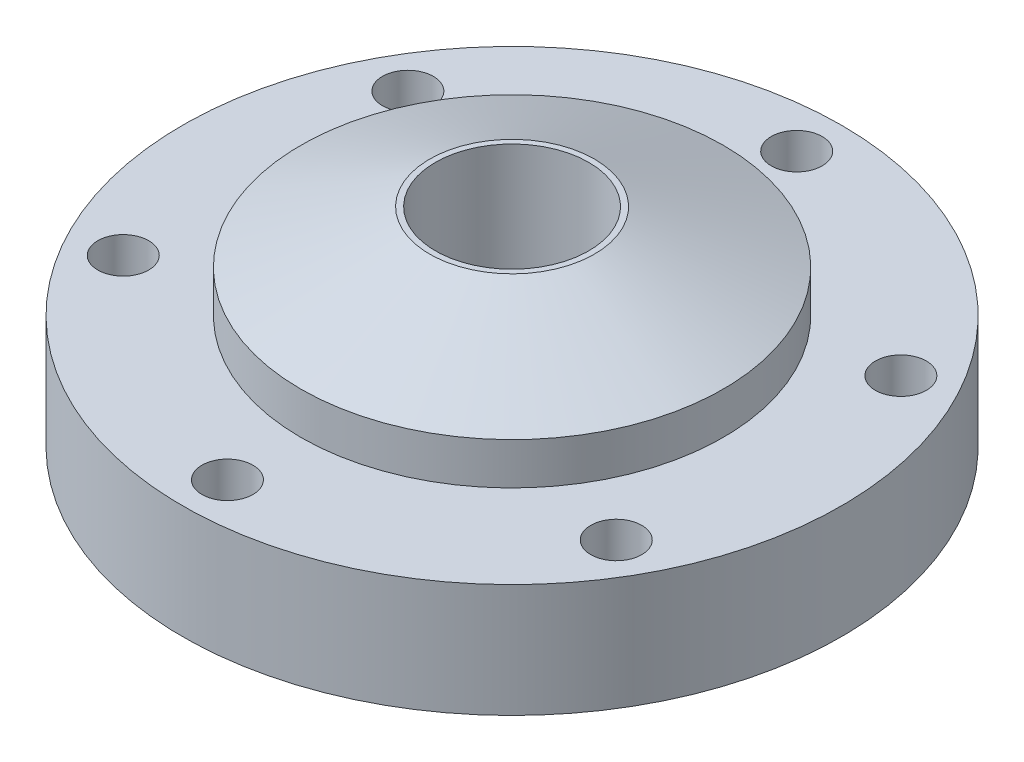
SolidWorks part; units mm, degrees
material "Hollow 3D Print"
ref_plane "Front Plane" through (0, 0, 0) normal (0, 0, 1) x (1, 0, 0)
ref_plane "Top Plane" through (0, 0, 0) normal (0, 1, 0) x (1, 0, 0)
ref_plane "Right Plane" through (0, 0, 0) normal (1, 0, 0) x (0, 0, -1)
sketch "Sketch1" plane through (0, 0, 0) normal (0, 0, 1) x (1, 0, 0)
  line L0 (0, 0) -> (0, 11.9562) construction
  line L1 (5.12, 5) -> (5.12, 13.8632)
  line L2 (5.12, 13.8632) -> (5.5, 13.8632)
  line L3 (5.5, 13.8632) -> (14.1, 10.3613)
  line L4 (14.1, 10.3613) -> (14.1, 7.5673)
  line L5 (14.1, 7.5673) -> (22, 7.5673)
  line L6 (22, 7.5673) -> (22, 0)
  line L7 (22, 0) -> (6.75, 0)
  line L8 (5.12, 5) -> (6.75, 5)
  line L9 (6.75, 5) -> (6.75, 0)
  dimension "D1" = 10.24
  dimension "D2" = 5
  dimension "D3" = 13.5
  dimension "D4" = 28.2
  dimension "D5" = 11
  dimension "D6" = 2.794
  dimension "D7" = 13.8632
  dimension "D8" = 7.5673
  dimension "D9" = 44
revolve "Revolve1" add sketch "Sketch1" angle 360 about L0
sketch "Sketch2" plane through (0, 7.5673, 0) normal (0, 1, 0) x (1, 0, 0)
  point P0 (0, 19)
  point P4 (16.4545, 9.5)
  point P5 (16.4545, -9.5)
  point P6 (0, -19)
  point P7 (-16.4545, -9.5)
  point P8 (-16.4545, 9.5)
  point P9 (0, 0)
  dimension "D2" = 38
  dimension "D1" = 6
hole_wizard "M3 Clearance Hole1" positions "Sketch2" profile "Sketch3" hole size "M3" standard "ANSI Metric" end condition up to next
sketch "Sketch3" plane through (0, 7.5673, -19) normal (1, 0, 0) x (0, 0, 1)
  line L0 (0, 0) -> (0, 7.5673)
  line L1 (0, 7.5673) -> (1.7, 7.5673)
  line L2 (1.7, 7.5673) -> (1.7, 0)
  line L5 (1.7, 0) -> (0, 0)
  line L11 (0, -6.35) -> (0, 107.95) construction
  dimension "Thru Hole Dia." = 3.4
  dimension "Thru Hole Depth" = 7.5673
